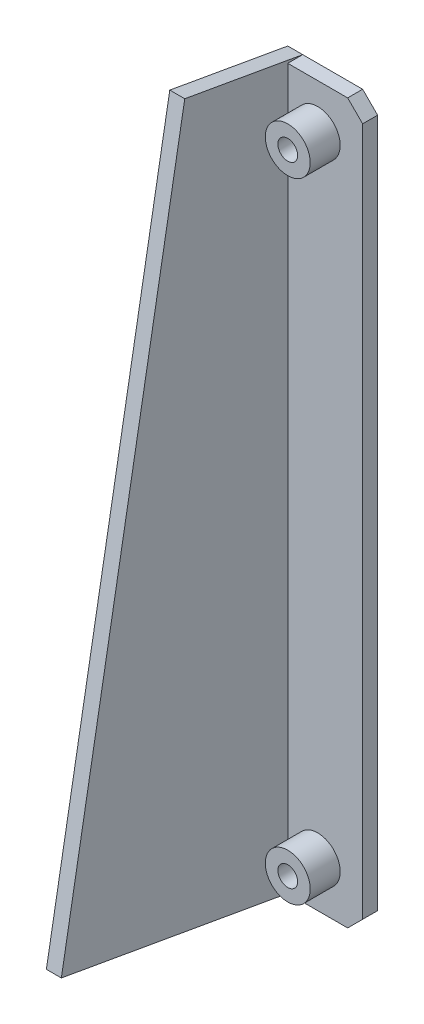
SolidWorks part; units mm, degrees
ref_plane "Front Plane" through (0, 0, 0) normal (0, 0, 1) x (1, 0, 0)
ref_plane "Top Plane" through (0, 0, 0) normal (0, 1, 0) x (1, 0, 0)
ref_plane "Right Plane" through (0, 0, 0) normal (1, 0, 0) x (0, 0, -1)
sketch "Sketch1" plane through (0, 0, 0) normal (0, 0, 1) x (1, 0, 0)
  line L1 (0, 0) -> (-9.525, 0)
  line L2 (0, 0) -> (0, 76.2)
  line L3 (0, 76.2) -> (-9.525, 76.2)
  line L4 (-9.525, 0) -> (-9.525, 76.2)
  dimension "D1" = 76.2
  dimension "D2" = 9.525
extrude "Boss-Extrude1" add sketch "Sketch1" along normal blind 1.5875
chamfer "Chamfer2" distance 1.5875 angle 45 4 edges at (0, 76.2, 0.7937) (-9.525, 76.2, 0.7937) (0, 0, 0.7937) (-9.525, 0, 0.7937)
hole_wizard "#97 (0.0825) Diameter Hole1" positions "Sketch2" profile "Sketch3" hole size "#97" standard "ANSI Inch" end condition through all
sketch "Sketch2" plane through (0, 0, 1.5875) normal (0, 0, 1) x (1, 0, 0)
  line L0 (-1.5875, 76.2) -> (-7.9375, 76.2) construction
  line L1 (-7.9375, 0) -> (-1.5875, 0) construction
  line L2 (0, 4.7625) -> (-9.525, 4.7625) construction
  line L3 (0, 1.5875) -> (0, 74.6125) construction
  line L4 (-9.525, 74.6125) -> (-9.525, 1.5875) construction
  point P0 (-4.7625, 4.7625)
  point P2 (-4.7625, 71.4375)
  dimension "D1" = 4.7625
  dimension "D2" = 4.7625
sketch "Sketch3" plane through (-4.7625, 4.7625, 1.5875) normal (1, 0, 0) x (0, -1, 0)
  line L0 (0, 0) -> (0, 1.5875)
  line L1 (0, 1.5875) -> (1.0477, 1.5875)
  line L2 (1.0477, 1.5875) -> (1.0477, 0)
  line L5 (1.0477, 0) -> (0, 0)
  line L11 (0, -6.35) -> (0, 107.95) construction
  dimension "Thru Hole Dia." = 2.0955
  dimension "Thru Hole Depth" = 1.5875
ref_plane "Plane1" through (0, 38.1, 0) normal (0, 1, 0) x (1, 0, 0)
sketch "Sketch5" plane through (0, 0, 1.5875) normal (0, 0, 1) x (1, 0, 0)
  line L0 (0.8731, 38.1) -> (-0.8731, 38.1) construction
  circle A0 centre (-4.7625, 4.7625) radius 1.0478
  circle A1 centre (-4.7625, 4.7625) radius 2.3813
  circle A2 centre (-4.7625, 71.4375) radius 2.3813
  circle A3 centre (-4.7625, 71.4375) radius 1.0477
  dimension "D1" = 4.7625
  dimension "D2" = 2.0955
extrude "Boss-Extrude2" add sketch "Sketch5" along normal blind 3.175
ref_plane "Plane2" through (0, 2.2977, 13.031) normal (0, -0.1736, -0.9848) x (-1, 0, 0)
sketch "Sketch7" plane through (0, 2.2977, 13.031) normal (0, -0.1736, -0.9848) x (-1, 0, 0)
  line L1 (9.525, 75.0424) -> (7.9375, 75.0424)
  line L2 (9.525, 75.0424) -> (9.525, -0.2757)
  line L3 (9.525, -0.2757) -> (7.9375, -0.2757)
  line L4 (7.9375, 75.0424) -> (7.9375, -0.2757)
  line L8 (1.5875, 75.0424) -> (7.9375, 75.0424) construction
  line L9 (9.525, 73.479) -> (9.525, 1.5634) construction
extrude "Boss-Extrude4" add sketch "Sketch7" along normal up to surface and the other way blind 12.7 up to face at (-3.7148, 4.7625, 0)
sketch "Sketch9" plane through (-7.9375, 0, 0) normal (1, 0, 0) x (0, 0, -1)
  line L0 (0, 0) -> (-1.5875, 0)
  line L1 (-1.5875, 0) -> (0, -0.2799)
  line L2 (0, -0.2799) -> (0, 0)
extrude "Cut-Extrude1" cut sketch "Sketch9" against normal through all
